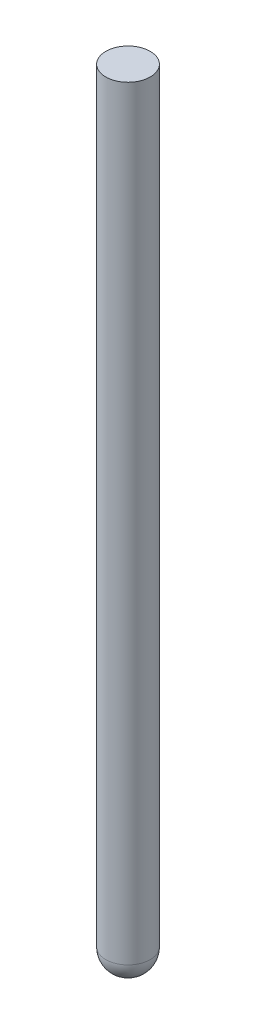
SolidWorks part; units mm, degrees
ref_plane "Front Plane" through (0, 0, 0) normal (0, 0, 1) x (1, 0, 0)
ref_plane "Top Plane" through (0, 0, 0) normal (0, 1, 0) x (1, 0, 0)
ref_plane "Right Plane" through (0, 0, 0) normal (1, 0, 0) x (0, 0, -1)
sketch "Sketch1" plane through (0, 0, 0) normal (0, 1, 0) x (1, 0, 0)
  circle A0 centre (0, 0) radius 5.0263
extrude "Boss-Extrude1" add sketch "Sketch1" along normal blind 177.8
fillet "Fillet1" radius 4.953 1 edges at (0, 0, 5.0263)
